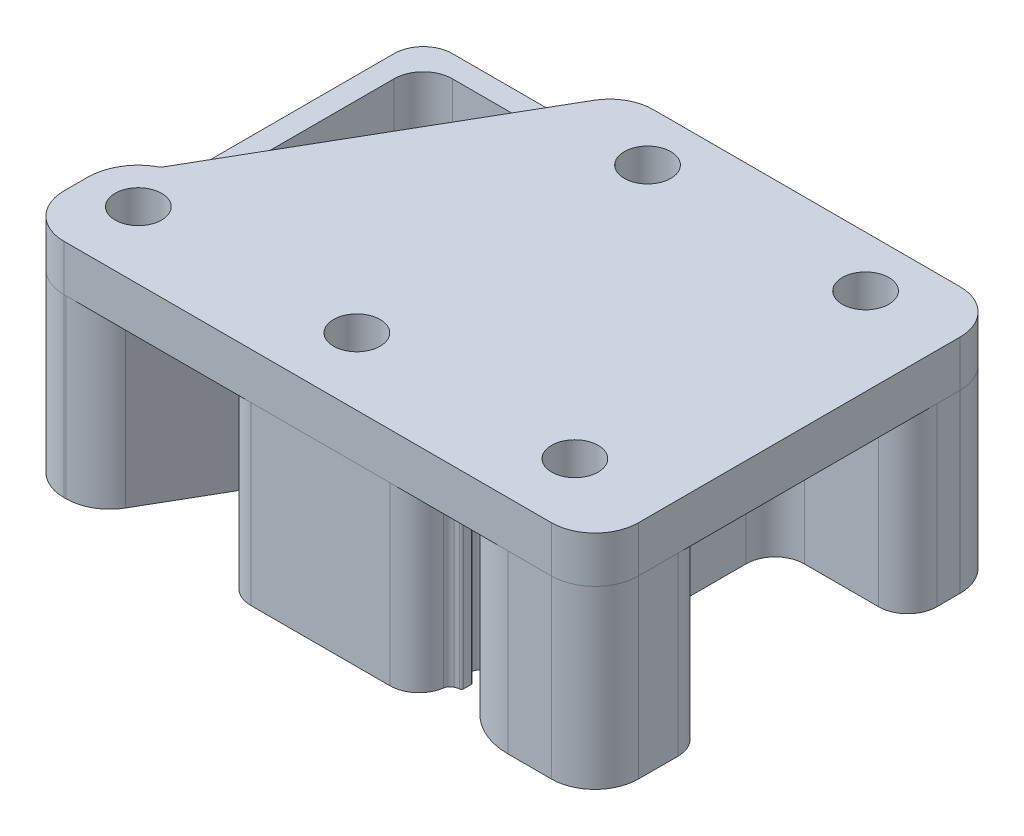
SolidWorks part; units mm, degrees
material "AISI 1045 Steel, cold drawn"
ref_plane "Front Plane" through (0, 0, 0) normal (0, 0, 1) x (1, 0, 0)
ref_plane "Top Plane" through (0, 0, 0) normal (0, 1, 0) x (1, 0, 0)
ref_plane "Right Plane" through (0, 0, 0) normal (1, 0, 0) x (0, 0, -1)
sketch "Sketch1" plane through (0, 0, 0) normal (0, 1, 0) x (1, 0, 0)
  line L0 (-13.5, -13.5) -> (-13.5, -14.619)
  line L1 (7.5, -10) -> (-7.5, -10) construction
  line L2 (7.5, -10) -> (7.5, 10) construction
  line L3 (7.5, 10) -> (-7.5, 10) construction
  line L4 (-7.5, -10) -> (-7.5, 10) construction
  line L5 (7.5, -10) -> (-7.5, 10) construction
  line L6 (7.5, 10) -> (-7.5, -10) construction
  line L7 (13.5, -13.5) -> (-13.5, -13.5) construction
  line L8 (13.5, -13.5) -> (13.5, 13.5)
  line L9 (13.5, 13.5) -> (-13.5, 13.5)
  line L10 (-13.5, -13.5) -> (-13.5, 13.5)
  line L11 (13.5, -13.5) -> (-13.5, 13.5) construction
  line L12 (13.5, 13.5) -> (-13.5, -13.5) construction
  line L13 (-13.5, -14.619) -> (13.5, -14.619)
  line L14 (13.5, -14.619) -> (13.5, -13.5)
  point P0 (0, 0)
  point P6 (0, 0)
  dimension "D1" = 15
  dimension "D2" = 27
  dimension "D3" = 1.119
  dimension "D4" = 20
extrude "Boss-Extrude1" add sketch "Sketch1" along normal mid plane 12.1
hole_wizard "M3 Clearance Hole1" positions "Sketch2" profile "Sketch3" hole size "M3" standard "ANSI Metric" end condition through all
sketch "Sketch2" plane through (0, 6.05, 0) normal (0, 1, 0) x (1, 0, 0)
  point P0 (-7.5, 10)
  point P3 (7.5, 10)
  point P6 (7.5, -10)
  point P9 (-7.5, -10)
sketch "Sketch3" plane through (-7.5, 6.05, -10) normal (1, 0, 0) x (0, 0, 1)
  line L0 (0, 0) -> (0, 12.1)
  line L1 (0, 12.1) -> (1.6, 12.1)
  line L2 (1.6, 12.1) -> (1.6, 0)
  line L5 (1.6, 0) -> (0, 0)
  line L11 (0, -6.35) -> (0, 107.95) construction
  dimension "Thru Hole Dia." = 3.2
  dimension "Thru Hole Depth" = 12.1
sketch "Sketch6" plane through (0, 6.05, 0) normal (0, 1, 0) x (1, 0, 0)
  line L0 (13.5, 13.5) -> (-13.5, 13.5) construction
  line L1 (-13.5, -14.619) -> (-28, -14.619)
  line L2 (-13.5, -14.619) -> (-13.5, 13.5)
  line L3 (-13.5, 13.5) -> (-28, 13.5)
  line L4 (-28, -14.619) -> (-28, 13.5)
  dimension "D1" = 28
extrude "Boss-Extrude3" add sketch "Sketch6" against normal up to surface (12.1 mm away) up to face at (-7.5, -6.05, -8.4)
sketch "Sketch8" plane through (0, 6.05, 0) normal (0, 1, 0) x (1, 0, 0)
  line L0 (-28, -14.619) -> (13.5, -14.619) construction
  line L2 (2.881, -10) -> (2.881, 4)
  line L3 (2.881, 4) -> (1.361, 4)
  line L4 (1.361, -14.619) -> (1.361, 4)
  line L5 (7.5, -14.619) -> (1.361, -14.619)
  arc A0 (2.881, -10) -> (7.5, -14.619) centre (7.5, -10) ccw
  dimension "D1" = 1.52
  dimension "D2" = 14
extrude "Cut-Extrude2" cut sketch "Sketch8" against normal up to surface (12.1 mm away) up to face at (-7.5, -6.05, -8.4)
sketch "Sketch9" plane through (0, 6.05, 0) normal (0, 1, 0) x (1, 0, 0)
  line L1 (2.881, 4) -> (6.306, 4)
  line L2 (2.881, 4) -> (2.881, -8)
  line L3 (2.881, -8) -> (6.306, -8)
  line L4 (6.306, 4) -> (6.306, -8)
  dimension "D1" = 3.425
  dimension "D2" = 12
extrude "Cut-Extrude3" cut sketch "Sketch9" against normal up to surface (12.1 mm away) up to face at (-7.5, -6.05, -8.4)
sketch "Sketch11" plane through (0, 6.05, 0) normal (0, 1, 0) x (1, 0, 0)
  line L1 (2.111, 0.7046) -> (2.111, 4.8734) construction
  line L4 (2.365, -998.8465) -> (2.365, 49001.1535) construction
  line L5 (2.111, 2.2598) -> (2.111, 2)
  line L6 (1.361, 3) -> (2.111, 3) construction
  line L7 (1.361, 4) -> (1.361, -14.619) construction
  line L8 (6.306, 4) -> (1.361, 4) construction
  line L9 (2.111, 2) -> (1.361, 2)
  line L10 (1.361, 2) -> (1.361, 4)
  line L11 (2.111, 4) -> (1.361, 4)
  line L12 (2.111, 3.7402) -> (2.111, 4)
  arc A2 (1.6728, 3.4989) -> (1.6728, 2.5011) centre (1.916, 3) ccw
  arc A4 (1.6728, 2.5011) -> (1.9806, 2.4085) centre (2.111, 3.4) ccw
  arc A5 (2.111, 2.2598) -> (1.9806, 2.4085) centre (1.961, 2.2598) ccw
  arc A6 (2.111, 3.7402) -> (1.9806, 3.5915) centre (1.961, 3.7402) cw
  arc A7 (1.6728, 3.4989) -> (1.9806, 3.5915) centre (2.111, 2.6) cw
  point P7 (1.361, 3)
  line M19 (1.361, -14.619) -> (1.361, 4)
  line M20 (1.361, 4) -> (6.306, 4)
  dimension "D3" = 0.555
  dimension "D4" = 1
  dimension "D5" = 1
  dimension "D6" = 0.15
  dimension "D1" = 0.254
  dimension "D2" = 0.75
  dimension "D7" = 1
extrude "Boss-Extrude4" add sketch "Sketch11" against normal up to surface (12.1 mm away) contours A2 A7 A6 L12 L10 M20 | L5 A5 A4 A2 L9 M19 region at (1.6833, 6.05, -3.7249) region at (1.6833, 6.05, -2.2751) up to face at (-7.5, -6.05, -8.4)
pattern_linear "LPattern1" count 9 spacing 2 along (0, 0, 1) of "Boss-Extrude4"
sketch "Sketch12" plane through (0, 6.05, 0) normal (0, 1, 0) x (1, 0, 0)
  circle A0 centre (2.111, 4) radius 0.5
  circle A1 centre (6.306, 4) radius 0.5
  circle A2 centre (6.306, -8) radius 0.5
  dimension "D1" = 1
extrude "Cut-Extrude5" cut sketch "Sketch12" against normal up to surface (12.1 mm away) up to face at (1.556, -6.05, 5.2005)
sketch "Sketch13" plane through (0, 6.05, 0) normal (0, 1, 0) x (1, 0, 0)
  line L3 (2.111, -14) -> (1.361, -14) construction
  line L4 (2.111, -13.7402) -> (2.111, -14) construction
  line L5 (2.111, -14) -> (1.361, -14)
  line L6 (2.111, -13.7402) -> (2.111, -14)
  line L7 (1.361, -14) -> (1.361, -13)
  arc A6 (1.6728, -12.5011) -> (1.6728, -13.4989) centre (1.916, -13) ccw construction
  arc A7 (1.6728, -13.4989) -> (1.9806, -13.5915) centre (2.111, -12.6) ccw construction
  arc A8 (2.111, -13.7402) -> (1.9806, -13.5915) centre (1.961, -13.7402) ccw construction
  arc A9 (1.361, -13) -> (1.6728, -13.4989) centre (1.916, -13) ccw
  arc A10 (1.6728, -13.4989) -> (1.9806, -13.5915) centre (2.111, -12.6) ccw
  arc A11 (2.111, -13.7402) -> (1.9806, -13.5915) centre (1.961, -13.7402) ccw
extrude "Cut-Extrude6" cut sketch "Sketch13" against normal up to surface (12.1 mm away) up to face at (1.6903, -6.05, 5.2284)
fillet "Fillet3" radius 0.5 7 edges at (5.806, 0, 8) (6.306, 0, 7.5) (5.806, 0, -4) (6.306, 0, -3.5) (2.611, 0, -4) (1.8595, 0, -3.5679) (2.881, 0, 8)
sketch "Sketch17" plane through (0, 6.05, 0) normal (0, 1, 0) x (1, 0, 0)
  line L0 (-21.1595, -14.619) -> (-15.513, -17.879)
  line L11 (-6.4019, 5.9019) -> (-3.8038, 4.4019) construction
  line L12 (-6.4019, 5.9019) -> (-2.9019, 11.9641) construction
  line L13 (-3.8038, 4.4019) -> (-0.3038, 10.4641) construction
  line L14 (-2.9019, 11.9641) -> (-0.3038, 10.4641) construction
  line L15 (-4.201, 12.7141) -> (0.9952, 9.7141) construction
  line L16 (-4.201, 12.7141) -> (-2.701, 15.3122) construction
  line L17 (0.9952, 9.7141) -> (2.4952, 12.3122) construction
  line L18 (-2.701, 15.3122) -> (2.4952, 12.3122) construction
  line L19 (-5.1029, 5.1519) -> (-0.1029, 13.8122) construction
  line L20 (-21.1595, -14.619) -> (-8.5843, 7.1619)
  line L21 (-15.513, -17.879) -> (-2.9378, 3.9019)
  line L22 (-8.5843, 7.1619) -> (-2.9378, 3.9019)
  line L23 (-22.5782, -10.8263) -> (-19.8719, -12.3888) construction
  line L24 (-22.5782, -10.8263) -> (-12.5782, 6.4942) construction
  line L25 (-19.8719, -12.3888) -> (-9.8719, 4.9317) construction
  line L26 (-12.5782, 6.4942) -> (-9.8719, 4.9317) construction
  line L27 (-28, -14.619) -> (1.361, -14.619) construction
  line L28 (-14.8719, -3.7285) -> (-17.5782, -2.166) construction
  circle A0 centre (-7.5, 10) radius 1.6 construction
  circle A1 centre (-7.5, -10) radius 1.6 construction
  dimension "D1" = 6.52
  dimension "D3" = 3
  dimension "D10" = 3
  dimension "D2" = 6
  dimension "D4" = 3
  dimension "D5" = 10
  dimension "D6" = 3.125
  dimension "D7" = 2.5
  dimension "D8" = 60
  dimension "D9" = 3
  dimension "D11" = 20
extrude "Cut-Extrude7" cut sketch "Sketch17" against normal up to surface (12.1 mm away) up to face at (1.9594, -6.05, 4.4571)
sketch "Sketch18" plane through (0, 6.05, 0) normal (0, 1, 0) x (1, 0, 0)
  line L0 (-26.0342, -14.619) -> (-26.0342, -10)
  line L2 (-14.1485, 10.3744) -> (-26.7237, -11.4065)
  line L3 (-12.344, 13.5) -> (-24.1063, -6.8729)
  line L4 (-12.344, 13.5) -> (-28, 13.5)
  line L5 (-28, 13.5) -> (-28, -14.619)
  line L7 (-28, -14.619) -> (-21.1595, -14.619) construction
  line L8 (-8.5843, 7.1619) -> (-21.1595, -14.619) construction
  line L10 (-28, -14.619) -> (-26.0342, -14.619)
  arc A2 (-24.1063, -6.8729) -> (-26.0342, -10) centre (-22.5342, -10) ccw
  point P0 (-7.5, -10)
  dimension "D2" = 3.5
  dimension "D1" = 6.425
extrude "Cut-Extrude8" cut sketch "Sketch18" against normal up to surface (12.1 mm away) contours A2 L10 | A2 L3 L4 L5 L10 region at (-22.8632, 6.05, -4.1187) up to face at (1.2277, -6.05, 4.4618)
hole_wizard "M3 Clearance Hole2" positions "Sketch19" profile "Sketch20" hole size "M3" standard "ANSI Metric" end condition up to next
sketch "Sketch19" plane through (0, 6.05, 0) normal (0, 1, 0) x (1, 0, 0)
  point P0 (-22.5342, -10)
sketch "Sketch20" plane through (-22.5342, 6.05, 10) normal (1, 0, 0) x (0, 0, 1)
  line L0 (0, 0) -> (0, 12.1)
  line L1 (0, 12.1) -> (1.6, 12.1)
  line L2 (1.6, 12.1) -> (1.6, 0)
  line L5 (1.6, 0) -> (0, 0)
  line L11 (0, -6.35) -> (0, 107.95) construction
  dimension "Thru Hole Dia." = 3.2
  dimension "Thru Hole Depth" = 12.1
fillet "Fillet4" radius 3 5 edges at (13.5, 0, 14.619) (13.5, 0, -13.5) (-12.344, 0, -13.5) (-26.0342, 0, 14.619) (-21.1595, 0, 14.619)
sketch "Sketch21" plane through (0, 6.05, 0) normal (0, 1, 0) x (1, 0, 0)
  line L0 (-8.5843, 7.1619) -> (-20.2935, -13.119) construction
  line L1 (-17.8343, -8.8595) -> (-20.8004, -7.147)
  line L2 (-17.8343, -8.8595) -> (-9.3343, 5.8629)
  line L3 (-20.8004, -7.147) -> (-12.3004, 7.5754)
  line L4 (-9.3343, 5.8629) -> (-12.3004, 7.5754)
  line L5 (-2.9378, 3.9019) -> (-8.5843, 7.1619) construction
  dimension "D3" = 17
  dimension "D1" = 3.425
  dimension "D2" = 1.5
extrude "Cut-Extrude9" cut sketch "Sketch21" against normal up to surface (12.1 mm away) up to face at (-22.5342, -6.05, 11.6)
sketch "Sketch22" plane through (0, 6.05, 0) normal (0, 1, 0) x (1, 0, 0)
  circle A0 centre (-20.8004, -7.147) radius 0.5
  circle A1 centre (-12.3004, 7.5754) radius 0.5
  circle A2 centre (-8.5843, 7.1619) radius 0.5
  circle A3 centre (-2.9378, 3.9019) radius 0.5
  arc A4 (2.544, 4.25) -> (1.6303, 3.8625) centre (2.111, 4) ccw construction
extrude "Cut-Extrude10" cut sketch "Sketch22" against normal up to surface (12.1 mm away) up to face at (-22.5342, -6.05, 11.6)
fillet "Fillet5" radius 0.5 10 edges at (-17.8343, 0, 8.8595) (-3.1878, 0, -3.4689) (-3.3708, 0, -4.1519) (-8.8343, 0, -6.7289) (-8.1513, 0, -6.9119) (-11.8674, 0, -7.3254) (-12.5504, 0, -7.1424) (-20.5504, 0, 6.714) (-20.3674, 0, 7.397) (-9.3343, 0, -5.8629)
ref_plane "Plane2" through (6.9551, 0, -12.0466) normal (0.5, 0, -0.866) x (-0.866, 0, -0.5)
sketch "Sketch29" plane through (0, 6.05, 0) normal (0, 1, 0) x (1, 0, 0)
  line L0 (-13.21, 12) -> (-24.1063, -6.8729) construction
  line L1 (-26.0342, -11.619) -> (-26.0342, -10) construction
  line L2 (13.5, -11.619) -> (13.5, 10.5) construction
  line L3 (10.5, 13.5) -> (-10.6119, 13.5) construction
  line L5 (-23.0342, -14.619) -> (10.5, -14.619)
  line L6 (-26.0342, -11.619) -> (-26.0342, -10)
  line L7 (13.5, -11.619) -> (13.5, 10.5)
  line L8 (10.5, 13.5) -> (-10.6119, 13.5)
  line L10 (-13.21, 12) -> (-24.1063, -6.8729)
  arc A0 (-24.1063, -6.8729) -> (-26.0342, -10) centre (-22.5342, -10) ccw construction
  arc A1 (-26.0342, -11.619) -> (-23.0342, -14.619) centre (-23.0342, -11.619) ccw construction
  arc A2 (10.5, -14.619) -> (13.5, -11.619) centre (10.5, -11.619) ccw construction
  arc A3 (13.5, 10.5) -> (10.5, 13.5) centre (10.5, 10.5) ccw construction
  arc A4 (-10.6119, 13.5) -> (-13.21, 12) centre (-10.6119, 10.5) ccw construction
  arc A5 (-24.1063, -6.8729) -> (-26.0342, -10) centre (-22.5342, -10) ccw
  arc A6 (-26.0342, -11.619) -> (-23.0342, -14.619) centre (-23.0342, -11.619) ccw
  arc A7 (10.5, -14.619) -> (13.5, -11.619) centre (10.5, -11.619) ccw
  arc A8 (13.5, 10.5) -> (10.5, 13.5) centre (10.5, 10.5) ccw
  arc A9 (-10.6119, 13.5) -> (-13.21, 12) centre (-10.6119, 10.5) ccw
  circle A12 centre (-22.5342, -10) radius 1.6 construction
  circle A13 centre (-7.5, -10) radius 1.6 construction
  circle A14 centre (7.5, -10) radius 1.6 construction
  circle A15 centre (7.5, 10) radius 1.6 construction
  circle A16 centre (-7.5, 10) radius 1.6 construction
  circle A17 centre (-22.5342, -10) radius 1.6
  circle A18 centre (-7.5, -10) radius 1.6
  circle A19 centre (7.5, -10) radius 1.6
  circle A20 centre (7.5, 10) radius 1.6
  circle A21 centre (-7.5, 10) radius 1.6
extrude "Boss-Extrude7" add sketch "Sketch29" along normal blind 3.175 separate body
hole_wizard "CBORE for M3 SHCS1" positions "Sketch23" profile "Sketch25" counterbore size "M3" standard "ANSI Metric" end condition up to next
sketch "Sketch23" plane through (6.9551, 0, -12.0466) normal (0.5, 0, -0.866) x (-0.866, 0, -0.5)
  line L0 (4.4952, -6.05) -> (9.4952, 6.05) construction
  line L1 (-2.3433, -6.05) -> (15.9402, -6.05) construction
  line L3 (-2.3433, 6.05) -> (15.9402, 6.05) construction
  point P15 (6.9952, 0)
  dimension "D1" = 5
sketch "Sketch25" plane through (0.8971, 0, -15.5442) normal (0, 1, 0) x (-0.866, 0, -0.5)
  line L0 (0, 0) -> (0, 12)
  line L1 (0, 12) -> (1.6, 12)
  line L3 (1.6, 12) -> (1.6, 6)
  line L4 (1.6, 6) -> (3.25, 6)
  line L5 (3.25, 6) -> (3.25, 0)
  line L7 (3.25, 0) -> (0, 0)
  line L11 (0, -6.35) -> (0, 107.95) construction
  dimension "Thru Hole Dia." = 3.2
  dimension "Thru Hole Depth" = 12
  dimension "C'Bore Dia." = 6.5
  dimension "C'Bore Depth" = 6
sketch "Sketch30" plane through (0, 6.05, 0) normal (0, 1, 0) x (1, 0, 0)
  line L1 (3.381, -8) -> (5.44, -8) construction
  line L2 (6.306, -7.134) -> (6.306, 3.134) construction
  line L3 (5.44, 4) -> (2.977, 4) construction
  line L4 (3.381, -8) -> (5.44, -8)
  line L5 (6.306, -7.134) -> (6.306, 3.134)
  line L6 (5.44, 4) -> (2.977, 4)
  line L7 (-18.0843, -9.2926) -> (-9.0843, 6.2959)
  line L8 (-20.0504, -7.5801) -> (-18.2673, -8.6095) construction
  line L9 (-12.7335, 6.8254) -> (-20.3674, -6.397) construction
  line L10 (-9.7673, 6.1129) -> (-11.5504, 7.1424) construction
  line L11 (-20.0504, -7.5801) -> (-18.2673, -8.6095)
  line L12 (-12.7335, 6.8254) -> (-20.3674, -6.397)
  line L13 (-9.7673, 6.1129) -> (-11.5504, 7.1424)
  line L14 (2.881, -8.5) -> (2.881, 4.0093)
  arc A0 (3.381, -8) -> (2.881, -8.5) centre (3.381, -8.5) ccw construction
  arc A1 (5.873, -8.25) -> (5.44, -8) centre (5.44, -8.5) ccw construction
  arc A2 (5.873, -8.25) -> (6.556, -7.567) centre (6.306, -8) ccw construction
  arc A3 (6.306, -7.134) -> (6.556, -7.567) centre (6.806, -7.134) ccw construction
  arc A4 (6.556, 3.567) -> (6.306, 3.134) centre (6.806, 3.134) ccw construction
  arc A5 (6.556, 3.567) -> (5.873, 4.25) centre (6.306, 4) ccw construction
  arc A6 (5.44, 4) -> (5.873, 4.25) centre (5.44, 4.5) ccw construction
  arc A7 (2.544, 4.25) -> (2.977, 4) centre (2.977, 4.5) ccw construction
  arc A8 (3.381, -8) -> (2.881, -8.5) centre (3.381, -8.5) ccw
  arc A9 (5.873, -8.25) -> (5.44, -8) centre (5.44, -8.5) ccw
  arc A10 (5.873, -8.25) -> (6.556, -7.567) centre (6.306, -8) ccw
  arc A11 (6.306, -7.134) -> (6.556, -7.567) centre (6.806, -7.134) ccw
  arc A12 (6.556, 3.567) -> (6.306, 3.134) centre (6.806, 3.134) ccw
  arc A13 (6.556, 3.567) -> (5.873, 4.25) centre (6.306, 4) ccw
  arc A14 (5.44, 4) -> (5.873, 4.25) centre (5.44, 4.5) ccw
  arc A15 (2.881, 4.0093) -> (2.977, 4) centre (2.977, 4.5) ccw
  arc A17 (-18.0843, -9.2926) -> (-18.2673, -8.6095) centre (-18.5173, -9.0426) ccw construction
  arc A18 (-20.0504, -7.5801) -> (-20.5504, -7.5801) centre (-20.3004, -8.0131) ccw construction
  arc A19 (-20.8004, -6.647) -> (-20.3674, -6.397) centre (-20.8004, -6.147) ccw construction
  arc A20 (-12.7335, 6.8254) -> (-12.7335, 7.3254) centre (-13.1665, 7.0754) ccw construction
  arc A21 (-11.8004, 7.5754) -> (-12.7335, 7.3254) centre (-12.3004, 7.5754) ccw construction
  arc A22 (-11.8004, 7.5754) -> (-11.5504, 7.1424) centre (-11.3004, 7.5754) ccw construction
  arc A23 (-9.7673, 6.1129) -> (-9.0843, 6.2959) centre (-9.5173, 6.5459) ccw construction
  arc A24 (-18.0843, -9.2926) -> (-18.2673, -8.6095) centre (-18.5173, -9.0426) ccw
  arc A25 (-20.0504, -7.5801) -> (-20.5504, -7.5801) centre (-20.3004, -8.0131) ccw
  arc A26 (-20.8004, -6.647) -> (-20.3674, -6.397) centre (-20.8004, -6.147) ccw
  arc A27 (-12.7335, 6.8254) -> (-12.7335, 7.3254) centre (-13.1665, 7.0754) ccw
  arc A28 (-11.8004, 7.5754) -> (-12.7335, 7.3254) centre (-12.3004, 7.5754) ccw
  arc A29 (-11.8004, 7.5754) -> (-11.5504, 7.1424) centre (-11.3004, 7.5754) ccw
  arc A30 (-9.7673, 6.1129) -> (-9.0843, 6.2959) centre (-9.5173, 6.5459) ccw
  arc A31 (-20.8004, -6.647) -> (-20.5504, -7.5801) centre (-20.8004, -7.147) ccw construction
  arc A32 (-20.8004, -6.647) -> (-20.5504, -7.5801) centre (-20.8004, -7.147) ccw
extrude "Boss-Extrude8" add sketch "Sketch30" against normal up to surface (12.1 mm away) up to face at (-22.5342, -6.05, 11.6)
fillet "Fillet6" radius 1 1 edges at (2.881, 0, -4.0093)
sketch "Sketch31" plane through (0, 6.05, 0) normal (0, 1, 0) x (1, 0, 0)
  line L0 (13.5, 6.9) -> (4.381, 6.9)
  line L2 (4.381, 6.9) -> (4.381, -6.9)
  line L3 (4.381, -6.9) -> (13.5, -6.9)
  line L4 (2.881, -10) -> (2.881, 3.4759) construction
  line L6 (13.5, 6.9) -> (13.5, -6.9)
  line L7 (13.5, -11.619) -> (13.5, 10.5) construction
  circle A0 centre (7.5, -10) radius 1.6 construction
  circle A1 centre (7.5, 10) radius 1.6 construction
  dimension "D1" = 3.1
  dimension "D2" = 3.1
  dimension "D3" = 1.5
extrude "Cut-Extrude11" cut sketch "Sketch31" against normal up to surface (12.1 mm away) up to face at (-0.8329, -6.05, 3.7569)
sketch "Sketch32" plane through (0, 6.05, 0) normal (0, 1, 0) x (1, 0, 0)
  line L0 (-10.0574, 7.6105) -> (-19.366, -8.5125)
  line L1 (-9.0173, 6.4119) -> (-20.2935, -13.119) construction
  line L2 (-13.21, 12) -> (-24.1063, -6.8729) construction
  line L3 (-13.21, 12) -> (-24.1063, -6.8729)
  line L5 (10.5, 13.5) -> (-10.6119, 13.5) construction
  line L6 (-7.5, 13.5) -> (-10.6119, 13.5)
  arc A0 (-19.366, -8.5125) -> (-24.1063, -6.8729) centre (-22.5342, -10) ccw
  arc A1 (-24.1063, -6.8729) -> (-26.0342, -10) centre (-22.5342, -10) ccw construction
  arc A2 (-7.5, 13.5) -> (-10.0574, 7.6105) centre (-7.5, 10) ccw
  arc A3 (-10.6119, 13.5) -> (-13.21, 12) centre (-10.6119, 10.5) ccw construction
  arc A4 (-10.6119, 13.5) -> (-13.21, 12) centre (-10.6119, 10.5) ccw
  dimension "D1" = 1.5
extrude "Cut-Extrude12" cut sketch "Sketch32" against normal up to surface (12.1 mm away) up to face at (-0.3561, -6.05, 3.5736)
sketch "Sketch34" plane through (0, -6.05, 0) normal (0, -1, 0) x (1, 0, 0)
  line L0 (0.111, -6.1826) -> (-7.4426, 6.9005)
  line L1 (-3.3708, -3.1519) -> (-13.6309, 14.619) construction
  line L2 (0.111, -6.1826) -> (0.111, 12.619)
  line L4 (0.111, 12.619) -> (-5.8414, 12.619)
  line L5 (2.111, 10.2598) -> (2.111, 9.7402) construction
  line L7 (-13.6309, 14.619) -> (1.361, 14.619) construction
  circle A2 centre (-7.5, 10) radius 3.1
  arc A3 (-7.4426, 6.9005) -> (-5.8414, 12.619) centre (-7.5, 10) ccw
  dimension "D2" = 1.5
  dimension "D3" = 2
  dimension "D4" = 2
  dimension "D1" = 1.5
extrude "Cut-Extrude14" cut sketch "Sketch34" against normal up to surface (12.1 mm away) up to face at (-0.2449, 6.05, 3.6119)
sketch "Sketch35" plane through (0, -6.05, 0) normal (0, -1, 0) x (1, 0, 0)
  line L0 (-4.9175, -11.9731) -> (0.7117, -8.7231) construction
  line L1 (-7.5622, -13.5) -> (1.2713, -8.4)
  line L2 (10.5, -13.5) -> (-7.5, -13.5) construction
  line L3 (1.2713, -8.4) -> (4.3871, -8.4)
  line L4 (7.5, -13.5) -> (-7.5622, -13.5)
  line L6 (4.381, -6.9) -> (13.5, -6.9) construction
  circle A1 centre (7.5, -10) radius 1.6 construction
  arc A3 (4.3871, -8.4) -> (7.5, -13.5) centre (7.5, -10) ccw
  dimension "D1" = 1.5
extrude "Cut-Extrude15" cut sketch "Sketch35" against normal up to surface (12.1 mm away) up to face at (-2.7337, 6.05, 6.3401)
fillet "Fillet7" radius 2 9 edges at (-13.6309, 0, 14.619) (1.361, 0, 14.619) (13.5, 0, 6.9) (4.381, 0, 6.9) (13.5, 0, -6.9) (4.381, 0, -6.9) (-19.366, 0, 8.5125) (-7.5612, 0, -13.4995) (-10.0574, 0, -7.6105)
fillet "Fillet8" radius 1 6 edges at (0.111, 0, 12.619) (0.111, 0, -6.1826) (-5.8414, 0, 12.619) (-7.4426, 0, 6.9005) (4.3871, 0, -8.4) (1.2713, 0, -8.4)
sketch "Sketch36" plane through (0, 6.05, 0) normal (0, 1, 0) x (1, 0, 0)
  line L0 (2.881, 4.4759) -> (2.881, 3.4759)
  line L1 (1.611, 4) -> (1.611, 4.4759)
  arc A0 (1.611, 4.4759) -> (2.881, 4.4759) centre (2.246, 4.4759) cw
  arc A3 (2.544, 4.25) -> (1.6303, 3.8625) centre (2.111, 4) ccw construction
  arc A4 (2.544, 4.25) -> (2.6117, 4.1586) centre (2.977, 4.5) ccw construction
  arc A5 (2.881, 3.4759) -> (2.6117, 4.1586) centre (1.881, 3.4759) ccw construction
  arc A6 (2.544, 4.25) -> (1.611, 4) centre (2.111, 4) ccw
  arc A7 (2.544, 4.25) -> (2.6117, 4.1586) centre (2.977, 4.5) ccw
  arc A8 (2.881, 3.4759) -> (2.6117, 4.1586) centre (1.881, 3.4759) ccw
  dimension "D1" = 1
extrude "Cut-Extrude16" cut sketch "Sketch36" against normal up to surface (12.1 mm away) up to face at (-2.9137, -6.05, 6.8822)
sketch "Sketch37" plane through (0, 6.05, 0) normal (0, 1, 0) x (1, 0, 0)
  line L0 (-10.6817, 6.5291) -> (-9.847, 7.9748)
  line L1 (-18.0522, -6.2369) -> (-10.6817, 6.5291) construction
  line L2 (1.0392, 8.534) -> (-6.9682, 13.1571) construction
  line L3 (-6.6764, 12.9886) -> (-6.9682, 13.1571)
  arc A0 (-6.6764, 12.9886) -> (-9.847, 7.9748) centre (-7.5, 10) ccw
  circle A1 centre (-7.5, 10) radius 1.6 construction
  arc A2 (-6.9682, 13.1571) -> (-8.5926, 13.3251) centre (-7.9682, 11.425) ccw construction
  arc A3 (-8.5926, 13.3251) -> (-10.6269, 8.4276) centre (-7.5, 10) ccw construction
  arc A4 (-10.6817, 6.5291) -> (-10.6269, 8.4276) centre (-12.4137, 7.5291) ccw construction
  arc A5 (-6.9682, 13.1571) -> (-8.5926, 13.3251) centre (-7.9682, 11.425) ccw
  arc A6 (-8.5926, 13.3251) -> (-10.6269, 8.4276) centre (-7.5, 10) ccw
  arc A7 (-10.6817, 6.5291) -> (-10.6269, 8.4276) centre (-12.4137, 7.5291) ccw
  dimension "D1" = 1.5
extrude "Cut-Extrude17" cut sketch "Sketch37" against normal up to surface (12.1 mm away) up to face at (-2.9137, -6.05, 6.8822)
fillet "Fillet9" radius 2 2 edges at (-6.6764, 0, -12.9886) (-9.847, 0, -7.9748)
sketch "Sketch38" plane through (0, 6.05, 0) normal (0, 1, 0) x (1, 0, 0)
  line L0 (-26.0342, -10) -> (-26.0342, 13.1)
  line L1 (-26.0342, 13.1) -> (-7.5, 13.1)
  line L2 (-24.5342, -7.1277) -> (-24.5342, 11.6)
  line L3 (-24.5342, 11.6) -> (-10.1552, 11.6)
  line L4 (-24.5342, -10) -> (-24.5342, 11.6) construction
  line L5 (-24.5342, 11.6) -> (-7.5, 11.6) construction
  arc A0 (-7.2093, 13.0863) -> (-10.3388, 8.7545) centre (-7.5, 10) ccw construction
  arc A1 (-7.5, 13.1) -> (-10.1552, 11.6) centre (-7.5, 10) ccw
  arc A2 (-20.7842, -6.9689) -> (-26.0342, -10) centre (-22.5342, -10) ccw construction
  arc A3 (-24.5342, -7.1277) -> (-26.0342, -10) centre (-22.5342, -10) ccw
  dimension "D1" = 1.5
extrude "Boss-Extrude9" add sketch "Sketch38" against normal up to surface (12.1 mm away) up to face at (-2.9137, -6.05, 6.8822)
fillet "Fillet10" radius 2 4 edges at (-24.5342, 0, 7.1277) (-10.1552, 0, -11.6) (-26.0342, 0, -13.1) (-24.5342, 0, -11.6)
sketch "Sketch39" plane through (0.9551, 0, -1.6543) normal (-0.5, 0, 0.866) x (0.866, 0, 0.5)
  circle A0 centre (-6.9952, 0) radius 1.6 construction
  circle A1 centre (-6.9952, 0) radius 1.6
extrude "Boss-Extrude10" add sketch "Sketch39" against normal up to surface (6 mm away) up to face at (-3.4885, 0, -11.1481)
